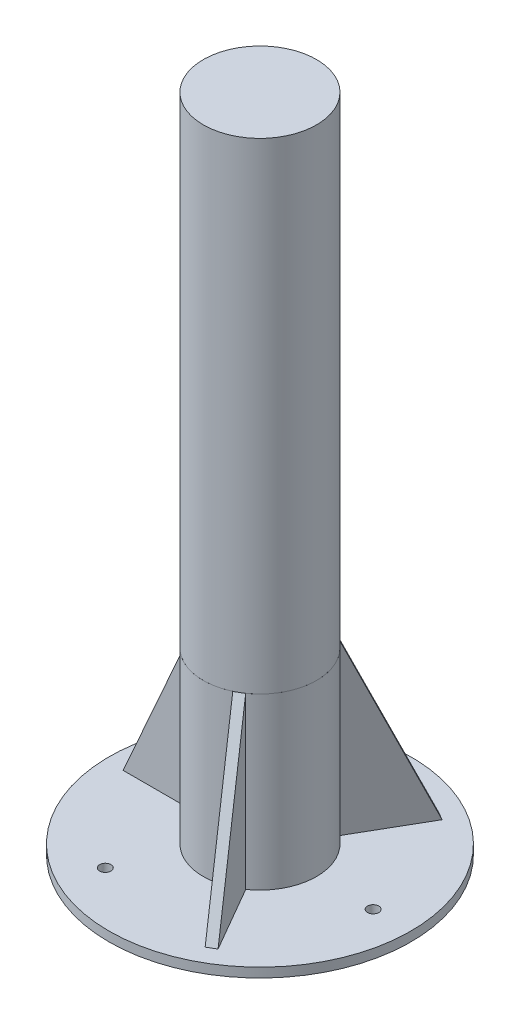
SolidWorks part; units mm, degrees
ref_plane "Front Plane" through (0, 0, 0) normal (0, 0, 1) x (1, 0, 0)
ref_plane "Top Plane" through (0, 0, 0) normal (0, 1, 0) x (1, 0, 0)
ref_plane "Right Plane" through (0, 0, 0) normal (1, 0, 0) x (0, 0, -1)
sketch "Sketch1" plane through (0, 0, 0) normal (0, 1, 0) x (1, 0, 0)
  circle A0 centre (0, 0) radius 80
  dimension "D1" = 160
extrude "Boss-Extrude1" add sketch "Sketch1" against normal blind 5
sketch "Sketch2" plane through (0, 0, 0) normal (0, 1, 0) x (1, 0, 0)
  circle A0 centre (0, 0) radius 30
  dimension "D1" = 60
extrude "Boss-Extrude2" add sketch "Sketch2" along normal blind 90 separate body
sketch "Sketch3" plane through (0, 90, 0) normal (0, 1, 0) x (1, 0, 0)
  circle A0 centre (0, 0) radius 30 construction
  circle A1 centre (0, 0) radius 30
extrude "Boss-Extrude3" add sketch "Sketch3" along normal blind 255 separate body
sketch "Sketch4" plane through (0, 0, 0) normal (0, 0, 1) x (1, 0, 0)
  line L0 (-70, 0) -> (-30, 0)
  line L1 (-30, 0) -> (-30, 90)
  line L2 (-30, 90) -> (-70, 0)
  line L3 (-30, 90) -> (-30, 0) construction
  line L4 (80, 0) -> (-80, 0) construction
  dimension "D1" = 40
  dimension "D2" = 90
  dimension "D3" = 0
  dimension "D4" = 0
extrude "Boss-Extrude4" add sketch "Sketch4" along normal blind 2.5 and the other way blind 2.5 separate body
pattern_circular "CirPattern1" count 3 every 120 about axis through (0, 90, 0) along (0, -1, 0) of "Boss-Extrude4"
sketch "Sketch5" plane through (0, 0, 0) normal (0, 1, 0) x (1, 0, 0)
  line L0 (32.8349, -61.8718) -> (12.8349, -27.2308) construction
  circle A0 centre (-30, 51.9615) radius 3
  circle A1 centre (0, 0) radius 30 construction
  circle A2 centre (60, 0) radius 3
  circle A3 centre (-30, -51.9615) radius 3
  point P12 (0, 0)
  dimension "D1" = 6
  dimension "D2" = 2.5
  dimension "D3" = 60
  dimension "D4" = 3
extrude "Cut-Extrude1" cut sketch "Sketch5" against normal through all
